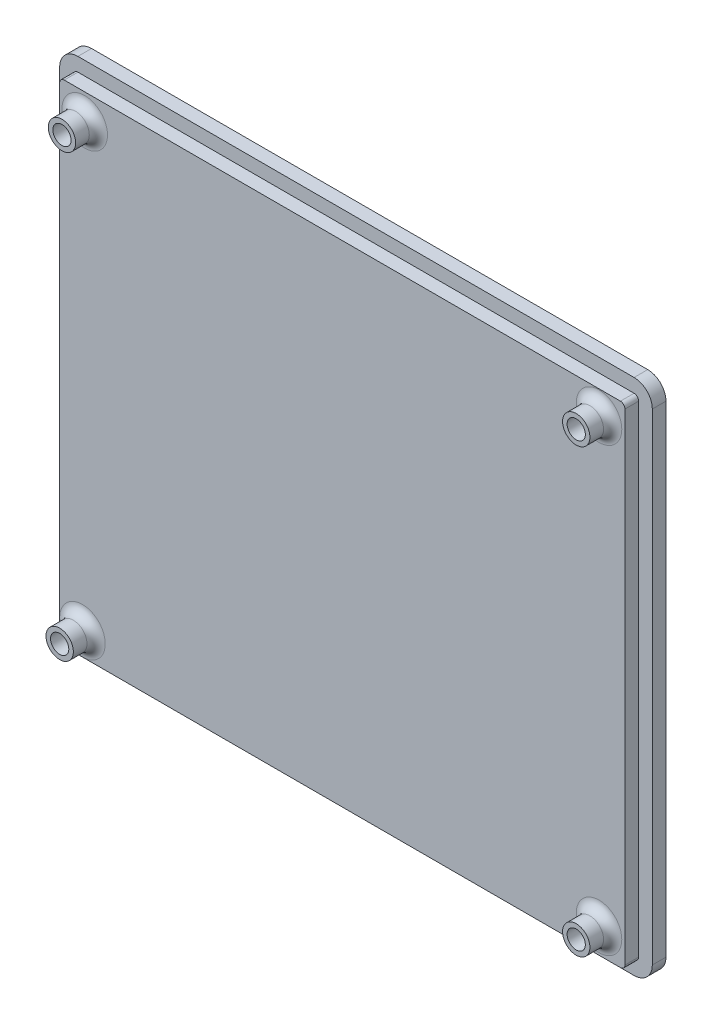
SolidWorks part; units mm, degrees
material "ABS"
ref_plane "Alzado" through (0, 0, 0) normal (0, 0, 1) x (1, 0, 0)
ref_plane "Planta" through (0, 0, 0) normal (0, 1, 0) x (1, 0, 0)
ref_plane "Vista lateral" through (0, 0, 0) normal (1, 0, 0) x (0, 0, -1)
sketch "Croquis4" plane through (0, 0, 0) normal (0, 0, 1) x (1, 0, 0)
  line L0 (-62.05, 53.85) -> (62.05, 53.85)
  line L1 (-60.05, 51.85) -> (60.05, 51.85)
  line L2 (-60.05, 51.85) -> (-60.05, -51.85)
  line L3 (-60.05, -51.85) -> (60.05, -51.85)
  line L4 (60.05, 51.85) -> (60.05, -51.85)
  line L5 (-60.05, 51.85) -> (60.05, -51.85) construction
  line L6 (-60.05, -51.85) -> (60.05, 51.85) construction
  line L7 (62.05, 53.85) -> (62.05, -53.85)
  line L8 (-62.05, -53.85) -> (62.05, -53.85)
  line L9 (-62.05, 53.85) -> (-62.05, -53.85)
  circle A0 centre (-56.55, 48.15) radius 2
  circle A1 centre (56.35, 48.65) radius 2
  circle A2 centre (-57.05, -48.85) radius 2
  circle A3 centre (56.35, -48.35) radius 2
  point P0 (0, 0)
  dimension "D3" = 4
  dimension "D4" = 3.7
  dimension "D5" = 3.5
  dimension "D6" = 3.7
  dimension "D7" = 3.2
  dimension "D8" = 3
  dimension "D9" = 3
  dimension "D10" = 3.7
  dimension "D11" = 3.5
  dimension "D12" = 113.4
  dimension "D1" = 120.1
  dimension "D2" = 103.7
  dimension "D13" = 2
extrude "Saliente-Extruir2" add sketch "Croquis4" along normal blind 6 contours A1 | A3 | L0 L7 L8 L9 | A0 | A2 region at (56.35, 48.65, 0) region at (56.35, -48.35, 0)
sketch "Croquis5" plane through (0, 0, 6) normal (0, 0, 1) x (1, 0, 0)
  line L4 (60.05, 51.85) -> (-60.05, 51.85)
  line L5 (60.05, -51.85) -> (60.05, 51.85)
  line L6 (-60.05, -51.85) -> (60.05, -51.85)
  line L7 (-60.05, 51.85) -> (-60.05, -51.85)
  line L8 (60.05, 51.85) -> (-60.05, 51.85)
  line L9 (60.05, -51.85) -> (60.05, 51.85)
  line L10 (-60.05, -51.85) -> (60.05, -51.85)
  line L11 (-60.05, 51.85) -> (-60.05, -51.85)
  line L12 (-62.05, -53.85) -> (62.05, -53.85)
  line L13 (-62.05, 53.85) -> (-62.05, -53.85)
  line L14 (62.05, 53.85) -> (-62.05, 53.85)
  line L15 (62.05, -53.85) -> (62.05, 53.85)
  line L16 (-62.05, -53.85) -> (62.05, -53.85)
  line L17 (-62.05, 53.85) -> (-62.05, -53.85)
  line L18 (62.05, 53.85) -> (-62.05, 53.85)
  line L19 (62.05, -53.85) -> (62.05, 53.85)
  circle A0 centre (-56.55, 48.15) radius 3
  circle A1 centre (56.35, -48.35) radius 2
  circle A2 centre (56.35, -48.35) radius 2
  circle A3 centre (-57.05, -48.85) radius 2
  circle A4 centre (-57.05, -48.85) radius 2
  circle A5 centre (56.35, 48.65) radius 2
  circle A6 centre (56.35, 48.65) radius 2
  circle A7 centre (-56.55, 48.15) radius 2
  circle A8 centre (-56.55, 48.15) radius 2
  circle A9 centre (56.35, 48.65) radius 3
  circle A10 centre (56.35, -48.35) radius 3
  circle A11 centre (-57.05, -48.85) radius 3
  circle M14 centre (56.35, 48.65) radius 2
  dimension "D1" = 0
  dimension "D2" = 0
  dimension "D3" = 0
  dimension "D4" = 0
  dimension "D5" = 0
  dimension "D6" = 0
  dimension "D7" = 1
extrude "Saliente-Extruir3" add sketch "Croquis5" along normal blind 5 contours M14 | A6 | A9 | A8 | A0 | A4 | A11 | A2 | A10 region at (56.35, 48.65, 6)
fillet "Redondeo1" radius 2 4 edges at (59.35, -48.35, 6) (-54.05, -48.85, 6) (-53.55, 48.15, 6) (59.35, 48.65, 6)
fillet "Redondeo2" radius 1 4 edges at (62.05, -53.85, 3) (-62.05, -53.85, 3) (-62.05, 53.85, 3) (62.05, 53.85, 3)
sketch "Croquis6" plane through (0, 0, 0) normal (0, 0, -1) x (-1, 0, 0)
  line L0 (61.05, 56.85) -> (-61.05, 56.85)
  line L1 (-65.05, 52.85) -> (-65.05, -52.85)
  line L2 (-61.05, -56.85) -> (61.05, -56.85)
  line L3 (65.05, -52.85) -> (65.05, 52.85)
  line L4 (-62.05, 52.85) -> (-62.05, -52.85)
  line L5 (-61.05, -53.85) -> (61.05, -53.85)
  line L6 (62.05, -52.85) -> (62.05, 52.85)
  line L7 (61.05, 53.85) -> (-61.05, 53.85)
  line L8 (-62.05, 52.85) -> (-62.05, -52.85)
  line L9 (-61.05, -53.85) -> (61.05, -53.85)
  line L10 (62.05, -52.85) -> (62.05, 52.85)
  line L11 (61.05, 53.85) -> (-61.05, 53.85)
  arc A0 (-61.05, 56.85) -> (-65.05, 52.85) centre (-61.05, 52.85) ccw
  arc A1 (-65.05, -52.85) -> (-61.05, -56.85) centre (-61.05, -52.85) ccw
  arc A2 (61.05, -56.85) -> (65.05, -52.85) centre (61.05, -52.85) ccw
  arc A3 (65.05, 52.85) -> (61.05, 56.85) centre (61.05, 52.85) ccw
  arc A4 (-62.05, -52.85) -> (-61.05, -53.85) centre (-61.05, -52.85) ccw
  arc A5 (61.05, -53.85) -> (62.05, -52.85) centre (61.05, -52.85) ccw
  arc A6 (62.05, 52.85) -> (61.05, 53.85) centre (61.05, 52.85) ccw
  arc A7 (-61.05, 53.85) -> (-62.05, 52.85) centre (-61.05, 52.85) ccw
  arc A8 (-62.05, -52.85) -> (-61.05, -53.85) centre (-61.05, -52.85) ccw
  arc A9 (61.05, -53.85) -> (62.05, -52.85) centre (61.05, -52.85) ccw
  arc A10 (62.05, 52.85) -> (61.05, 53.85) centre (61.05, 52.85) ccw
  arc A11 (-61.05, 53.85) -> (-62.05, 52.85) centre (-61.05, 52.85) ccw
  dimension "D3" = 4
  dimension "D1" = 0
  dimension "D2" = 3
extrude "Saliente-Extruir4" add sketch "Croquis6" against normal blind 3
